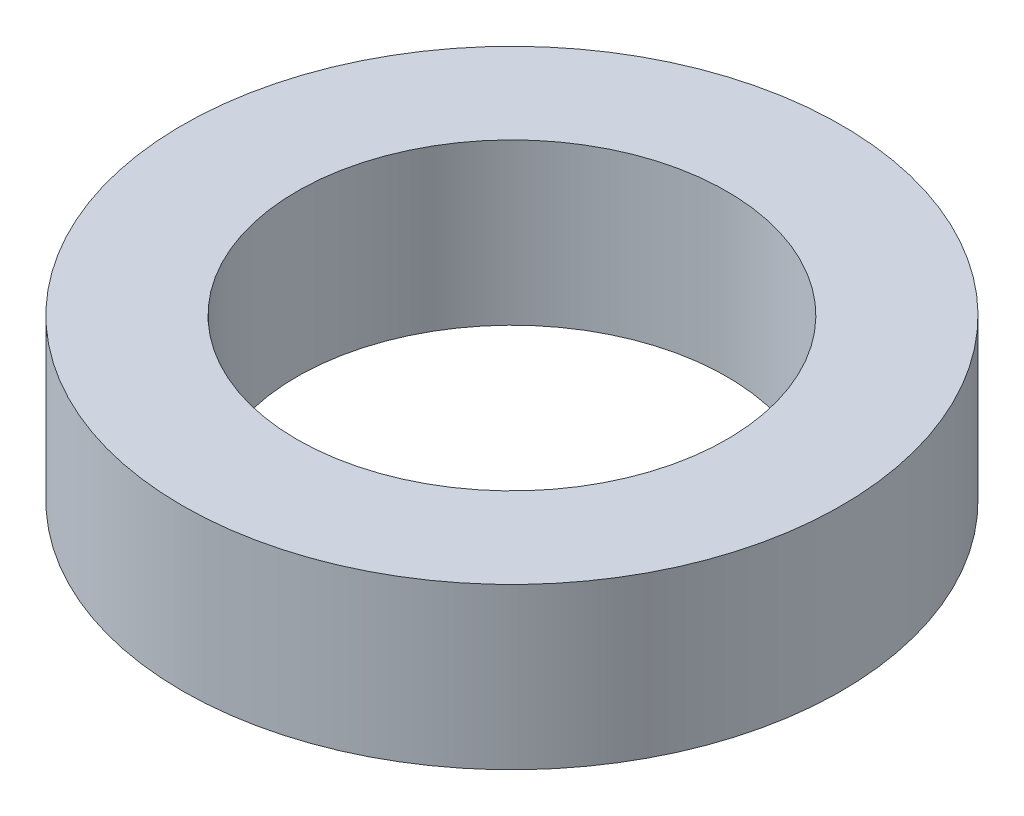
SolidWorks part; units mm, degrees
ref_plane "Front Plane" through (0, 0, 0) normal (0, 0, 1) x (1, 0, 0)
ref_plane "Top Plane" through (0, 0, 0) normal (0, 1, 0) x (1, 0, 0)
ref_plane "Right Plane" through (0, 0, 0) normal (1, 0, 0) x (0, 0, -1)
sketch "Sketch1" plane through (0, 0, 0) normal (0, 1, 0) x (1, 0, 0)
  circle A0 centre (0, 0) radius 57.5
  dimension "FLANGE_OD" = 115
extrude "Boss-Extrude1" add sketch "Sketch1" along normal blind 28
sketch "Sketch2" plane through (0, 0, 0) normal (0, 1, 0) x (1, 0, 0)
  circle A0 centre (0, 0) radius 37.5
  dimension "BORE_D" = 75
extrude "Cut-Extrude1" cut sketch "Sketch2" along normal through all
sketch "Sketch3" plane through (0, 28, 0) normal (0, 1, 0) x (1, 0, 0)
  circle A0 centre (0, 0) radius 22.5469 construction
  circle A1 centre (-22.5469, 0) radius 3.3365
  dimension "BOLT_D" = 6.6731
  dimension "BOLT_PCD" = 45.0939
extrude "Cut-Extrude2" cut sketch "Sketch3" against normal blind 27.9184 rebuild error yes
pattern_circular "CirPattern1" count 6 over 360 rebuild error yes
